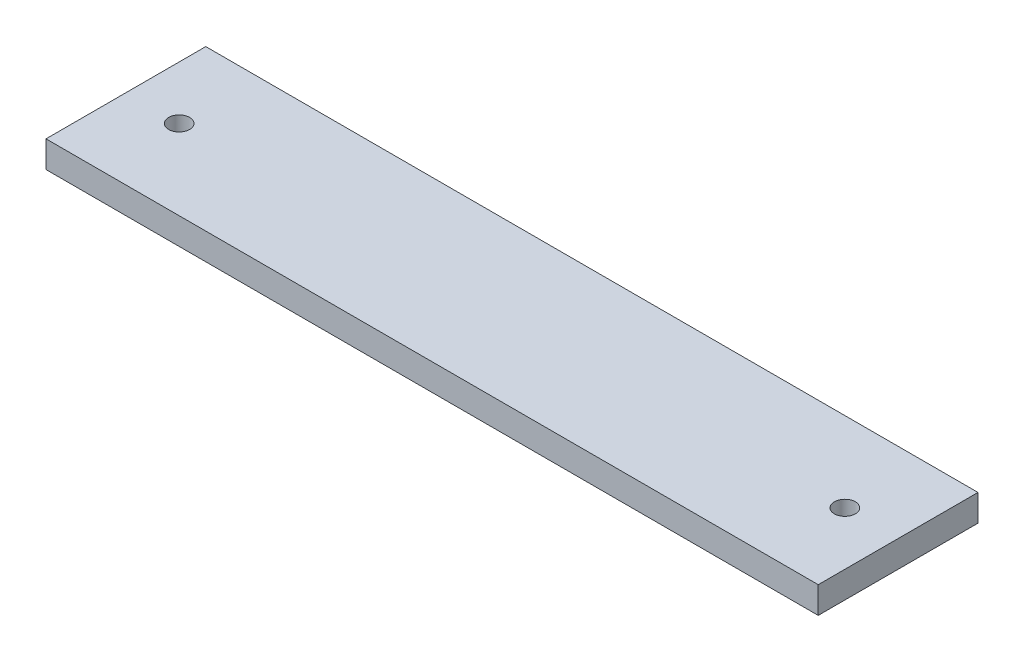
SolidWorks part; units mm, degrees
ref_plane "Front Plane" through (0, 0, 0) normal (0, 0, 1) x (1, 0, 0)
ref_plane "Top Plane" through (0, 0, 0) normal (0, 1, 0) x (1, 0, 0)
ref_plane "Right Plane" through (0, 0, 0) normal (1, 0, 0) x (0, 0, -1)
sketch "Sketch1" plane through (0, 0, 0) normal (0, 1, 0) x (1, 0, 0)
  line L0 (0, 19.05) -> (12.7, 19.05)
  line L1 (0, 0) -> (184.15, 0)
  line L2 (0, 0) -> (0, 38.1)
  line L3 (0, 38.1) -> (184.15, 38.1)
  line L4 (184.15, 0) -> (184.15, 38.1)
  line L5 (184.15, 19.05) -> (171.45, 19.05)
  circle A0 centre (12.7, 19.05) radius 2.5
  circle A1 centre (12.7, 19.05) radius 7 construction
  circle A2 centre (171.45, 19.05) radius 2.5
  circle A3 centre (171.45, 19.05) radius 7 construction
  dimension "D4" = 5
  dimension "D5" = 14
  dimension "D7" = 5
  dimension "D8" = 14
  dimension "D1" = 184.15
  dimension "D2" = 38.1
  dimension "D3" = 12.7
  dimension "D6" = 12.7
extrude "Boss-Extrude1" add sketch "Sketch1" along normal blind 6.35 contours A3 L4 L3 L2 A0 L1 region at (92.075, 0, -19.05)
